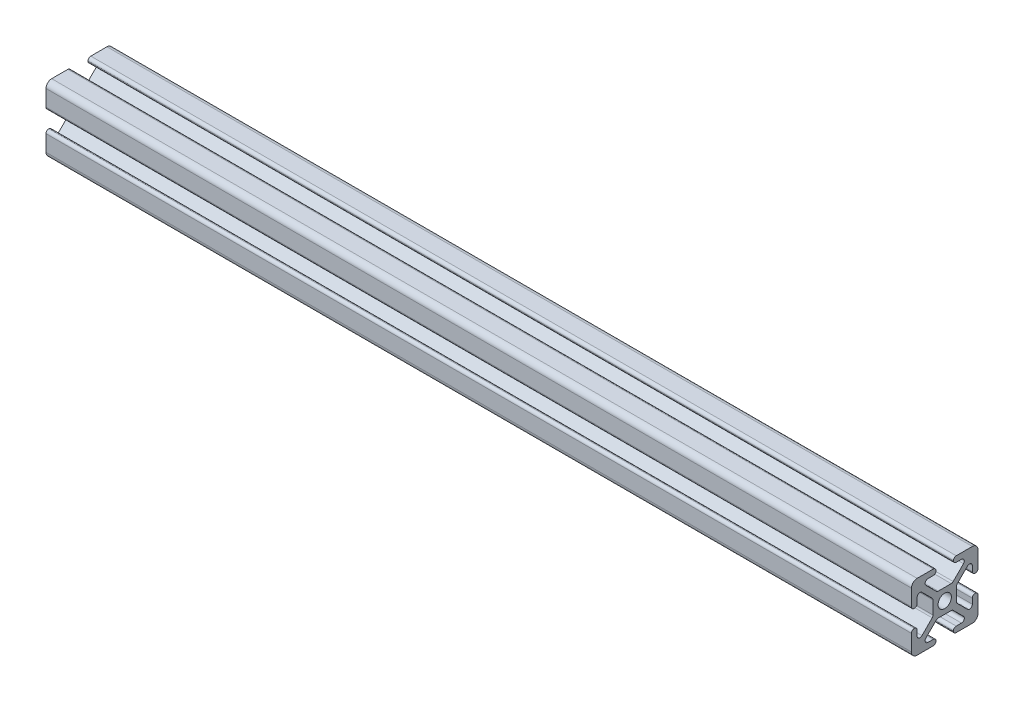
SolidWorks part; units mm, degrees
ref_plane "Front Plane" through (0, 0, 0) normal (1, 0, 0) x (0, 1, 0)
ref_plane "Top Plane" through (0, 0, 0) normal (0, 0, 1) x (0, 1, 0)
ref_plane "Right Plane" through (0, 0, 0) normal (0, 1, 0) x (-1, 0, 0)
sketch "Sketch1" plane through (0, 0, 0) normal (1, 0, 0) x (0, 1, 0)
  line L0 (0, 0) -> (0, 12.5) construction
  line L1 (-12.5, -12.5) -> (12.5, -12.5)
  line L2 (-12.5, -12.5) -> (-12.5, 12.5)
  line L3 (-12.5, 12.5) -> (12.5, 12.5)
  line L4 (12.5, -12.5) -> (12.5, 12.5)
  line L5 (-12.5, -12.5) -> (12.5, 12.5) construction
  line L6 (-12.5, 12.5) -> (12.5, -12.5) construction
  line L7 (-3.25, 12.5) -> (-3.25, 10.37)
  line L8 (-3.25, 10.37) -> (-8.8639, 10.37)
  line L9 (-8.8639, 10.37) -> (-2.8739, 4.38)
  line L10 (-2.8739, 4.38) -> (2.8739, 4.38)
  line L11 (8.8639, 10.37) -> (2.8739, 4.38)
  line L12 (3.25, 10.37) -> (8.8639, 10.37)
  line L13 (3.25, 12.5) -> (3.25, 10.37)
  line L14 (12.5, -3.25) -> (10.37, -3.25)
  line L15 (10.37, -3.25) -> (10.37, -8.8639)
  line L16 (10.37, -8.8639) -> (4.38, -2.8739)
  line L17 (4.38, 2.8739) -> (4.38, -2.8739)
  line L18 (10.37, 8.8639) -> (4.38, 2.8739)
  line L19 (10.37, 3.25) -> (10.37, 8.8639)
  line L20 (12.5, 3.25) -> (10.37, 3.25)
  line L21 (-3.25, -12.5) -> (-3.25, -10.37)
  line L22 (-3.25, -10.37) -> (-8.8639, -10.37)
  line L23 (-8.8639, -10.37) -> (-2.8739, -4.38)
  line L24 (2.8739, -4.38) -> (-2.8739, -4.38)
  line L25 (8.8639, -10.37) -> (2.8739, -4.38)
  line L26 (3.25, -10.37) -> (8.8639, -10.37)
  line L27 (3.25, -12.5) -> (3.25, -10.37)
  line L28 (-12.5, 3.25) -> (-10.37, 3.25)
  line L29 (-10.37, 3.25) -> (-10.37, 8.8639)
  line L30 (-10.37, 8.8639) -> (-4.38, 2.8739)
  line L31 (-4.38, -2.8739) -> (-4.38, 2.8739)
  line L32 (-10.37, -8.8639) -> (-4.38, -2.8739)
  line L33 (-10.37, -3.25) -> (-10.37, -8.8639)
  line L34 (-12.5, -3.25) -> (-10.37, -3.25)
  circle A0 centre (0, 0) radius 2.5
  point P0 (0, 0)
  point P15 (0, 4.38)
  dimension "D3" = 5
  dimension "D1" = 25
  dimension "D2" = 25
  dimension "D4" = 2.13
  dimension "D5" = 2.13
  dimension "D6" = 6.5
  dimension "D7" = 4.38
  dimension "D8" = 4
extrude "Boss-Extrude1" add sketch "Sketch1" along normal blind 325 contours L34 L2 L1 L21 L22 L23 L24 L25 L26 L27 L4 L14 L15 L16 L17 L18 L19 L20 L3 L13 L12 L11 L10 L9 L8 L7 L28 L29 L30 L31 L32 L33 A0 region at (0, -12.1464, -7.875)
fillet "Fillet1" radius 1.065 32 edges at (162.5, -10.37, -8.8639) (162.5, 2.8739, -4.38) (162.5, -2.8739, -4.38) (162.5, -4.38, 2.8739) (162.5, -4.38, -2.8739) (162.5, -2.8739, 4.38) (162.5, 2.8739, 4.38) (162.5, 4.38, 2.8739) (162.5, 4.38, -2.8739) (162.5, -8.8639, -10.37) (162.5, 8.8639, -10.37) (162.5, 10.37, -8.8639) (162.5, -10.37, 8.8639) (162.5, -8.8639, 10.37) (162.5, 10.37, 8.8639) (162.5, 8.8639, 10.37) (162.5, 12.5, 3.25) (162.5, -3.25, -12.5) (162.5, -10.37, 3.25) (162.5, 10.37, 3.25) (162.5, -10.37, -3.25) (162.5, -12.5, -3.25) (162.5, -12.5, 3.25) (162.5, 3.25, -10.37) (162.5, -3.25, -10.37) (162.5, 3.25, -12.5) (162.5, 10.37, -3.25) (162.5, 12.5, -3.25) (162.5, 3.25, 12.5) (162.5, 3.25, 10.37) (162.5, -3.25, 10.37) (162.5, -3.25, 12.5)
fillet "Fillet2" radius 2.13 4 edges at (162.5, 12.5, -12.5) (162.5, -12.5, -12.5) (162.5, 12.5, 12.5) (162.5, -12.5, 12.5)
sketch "Sketch2" plane through (325, 0, 0) normal (1, 0, 0) x (0, 1, 0)
  line L0 (10.37, -12.5) -> (4.315, -12.5)
  line L1 (10.37, -12.5) -> (4.315, -12.5)
  line L2 (4.315, -10.37) -> (6.2927, -10.37)
  line L3 (4.315, -10.37) -> (6.2927, -10.37)
  line L4 (7.0458, -8.5519) -> (3.1858, -4.6919)
  line L5 (7.0458, -8.5519) -> (3.1858, -4.6919)
  line L6 (2.4327, -4.38) -> (-2.4327, -4.38)
  line L7 (2.4327, -4.38) -> (-2.4327, -4.38)
  line L8 (-3.1858, -4.6919) -> (-7.0458, -8.5519)
  line L9 (-3.1858, -4.6919) -> (-7.0458, -8.5519)
  line L10 (-6.2927, -10.37) -> (-4.315, -10.37)
  line L11 (-6.2927, -10.37) -> (-4.315, -10.37)
  line L12 (-4.315, -12.5) -> (-10.37, -12.5)
  line L13 (-4.315, -12.5) -> (-10.37, -12.5)
  line L14 (-12.5, -10.37) -> (-12.5, -4.315)
  line L15 (-12.5, -10.37) -> (-12.5, -4.315)
  line L16 (-10.37, -4.315) -> (-10.37, -6.2927)
  line L17 (-10.37, -4.315) -> (-10.37, -6.2927)
  line L18 (-8.5519, -7.0458) -> (-4.6919, -3.1858)
  line L19 (-8.5519, -7.0458) -> (-4.6919, -3.1858)
  line L20 (-4.38, -2.4327) -> (-4.38, 2.4327)
  line L21 (-4.38, -2.4327) -> (-4.38, 2.4327)
  line L22 (-4.6919, 3.1858) -> (-8.5519, 7.0458)
  line L23 (-4.6919, 3.1858) -> (-8.5519, 7.0458)
  line L24 (-10.37, 6.2927) -> (-10.37, 4.315)
  line L25 (-10.37, 6.2927) -> (-10.37, 4.315)
  line L26 (-12.5, 4.315) -> (-12.5, 10.37)
  line L27 (-12.5, 4.315) -> (-12.5, 10.37)
  line L28 (-10.37, 12.5) -> (-4.315, 12.5)
  line L29 (-10.37, 12.5) -> (-4.315, 12.5)
  line L30 (-4.315, 10.37) -> (-6.2927, 10.37)
  line L31 (-4.315, 10.37) -> (-6.2927, 10.37)
  line L32 (-7.0458, 8.5519) -> (-3.1858, 4.6919)
  line L33 (-7.0458, 8.5519) -> (-3.1858, 4.6919)
  line L34 (-2.4327, 4.38) -> (2.4327, 4.38)
  line L35 (-2.4327, 4.38) -> (2.4327, 4.38)
  line L36 (3.1858, 4.6919) -> (7.0458, 8.5519)
  line L37 (3.1858, 4.6919) -> (7.0458, 8.5519)
  line L38 (6.2927, 10.37) -> (4.315, 10.37)
  line L39 (6.2927, 10.37) -> (4.315, 10.37)
  line L40 (4.315, 12.5) -> (10.37, 12.5)
  line L41 (4.315, 12.5) -> (10.37, 12.5)
  line L42 (12.5, 10.37) -> (12.5, 4.315)
  line L43 (12.5, 10.37) -> (12.5, 4.315)
  line L44 (10.37, 4.315) -> (10.37, 6.2927)
  line L45 (10.37, 4.315) -> (10.37, 6.2927)
  line L46 (8.5519, 7.0458) -> (4.6919, 3.1858)
  line L47 (8.5519, 7.0458) -> (4.6919, 3.1858)
  line L48 (4.38, 2.4327) -> (4.38, -2.4327)
  line L49 (4.38, 2.4327) -> (4.38, -2.4327)
  line L50 (4.6919, -3.1858) -> (8.5519, -7.0458)
  line L51 (4.6919, -3.1858) -> (8.5519, -7.0458)
  line L52 (10.37, -6.2927) -> (10.37, -4.315)
  line L53 (10.37, -6.2927) -> (10.37, -4.315)
  line L54 (12.5, -4.315) -> (12.5, -10.37)
  line L55 (12.5, -4.315) -> (12.5, -10.37)
  arc A0 (10.37, -12.5) -> (12.5, -10.37) centre (10.37, -10.37) ccw
  circle A1 centre (0, 0) radius 2.5
  circle A2 centre (0, 0) radius 2.5
  arc A3 (10.37, -12.5) -> (12.5, -10.37) centre (10.37, -10.37) ccw
  arc A4 (3.25, -11.435) -> (4.315, -12.5) centre (4.315, -11.435) ccw
  arc A5 (3.25, -11.435) -> (4.315, -12.5) centre (4.315, -11.435) ccw
  arc A6 (4.315, -10.37) -> (3.25, -11.435) centre (4.315, -11.435) ccw
  arc A7 (4.315, -10.37) -> (3.25, -11.435) centre (4.315, -11.435) ccw
  arc A8 (6.2927, -10.37) -> (7.0458, -8.5519) centre (6.2927, -9.305) ccw
  arc A9 (6.2927, -10.37) -> (7.0458, -8.5519) centre (6.2927, -9.305) ccw
  arc A10 (3.1858, -4.6919) -> (2.4327, -4.38) centre (2.4327, -5.445) ccw
  arc A11 (3.1858, -4.6919) -> (2.4327, -4.38) centre (2.4327, -5.445) ccw
  arc A12 (-2.4327, -4.38) -> (-3.1858, -4.6919) centre (-2.4327, -5.445) ccw
  arc A13 (-2.4327, -4.38) -> (-3.1858, -4.6919) centre (-2.4327, -5.445) ccw
  arc A14 (-7.0458, -8.5519) -> (-6.2927, -10.37) centre (-6.2927, -9.305) ccw
  arc A15 (-7.0458, -8.5519) -> (-6.2927, -10.37) centre (-6.2927, -9.305) ccw
  arc A16 (-3.25, -11.435) -> (-4.315, -10.37) centre (-4.315, -11.435) ccw
  arc A17 (-3.25, -11.435) -> (-4.315, -10.37) centre (-4.315, -11.435) ccw
  arc A18 (-4.315, -12.5) -> (-3.25, -11.435) centre (-4.315, -11.435) ccw
  arc A19 (-4.315, -12.5) -> (-3.25, -11.435) centre (-4.315, -11.435) ccw
  arc A20 (-12.5, -10.37) -> (-10.37, -12.5) centre (-10.37, -10.37) ccw
  arc A21 (-12.5, -10.37) -> (-10.37, -12.5) centre (-10.37, -10.37) ccw
  arc A22 (-11.435, -3.25) -> (-12.5, -4.315) centre (-11.435, -4.315) ccw
  arc A23 (-11.435, -3.25) -> (-12.5, -4.315) centre (-11.435, -4.315) ccw
  arc A24 (-10.37, -4.315) -> (-11.435, -3.25) centre (-11.435, -4.315) ccw
  arc A25 (-10.37, -4.315) -> (-11.435, -3.25) centre (-11.435, -4.315) ccw
  arc A26 (-10.37, -6.2927) -> (-8.5519, -7.0458) centre (-9.305, -6.2927) ccw
  arc A27 (-10.37, -6.2927) -> (-8.5519, -7.0458) centre (-9.305, -6.2927) ccw
  arc A28 (-4.6919, -3.1858) -> (-4.38, -2.4327) centre (-5.445, -2.4327) ccw
  arc A29 (-4.6919, -3.1858) -> (-4.38, -2.4327) centre (-5.445, -2.4327) ccw
  arc A30 (-4.38, 2.4327) -> (-4.6919, 3.1858) centre (-5.445, 2.4327) ccw
  arc A31 (-4.38, 2.4327) -> (-4.6919, 3.1858) centre (-5.445, 2.4327) ccw
  arc A32 (-8.5519, 7.0458) -> (-10.37, 6.2927) centre (-9.305, 6.2927) ccw
  arc A33 (-8.5519, 7.0458) -> (-10.37, 6.2927) centre (-9.305, 6.2927) ccw
  arc A34 (-11.435, 3.25) -> (-10.37, 4.315) centre (-11.435, 4.315) ccw
  arc A35 (-11.435, 3.25) -> (-10.37, 4.315) centre (-11.435, 4.315) ccw
  arc A36 (-12.5, 4.315) -> (-11.435, 3.25) centre (-11.435, 4.315) ccw
  arc A37 (-12.5, 4.315) -> (-11.435, 3.25) centre (-11.435, 4.315) ccw
  arc A38 (-10.37, 12.5) -> (-12.5, 10.37) centre (-10.37, 10.37) ccw
  arc A39 (-10.37, 12.5) -> (-12.5, 10.37) centre (-10.37, 10.37) ccw
  arc A40 (-3.25, 11.435) -> (-4.315, 12.5) centre (-4.315, 11.435) ccw
  arc A41 (-3.25, 11.435) -> (-4.315, 12.5) centre (-4.315, 11.435) ccw
  arc A42 (-4.315, 10.37) -> (-3.25, 11.435) centre (-4.315, 11.435) ccw
  arc A43 (-4.315, 10.37) -> (-3.25, 11.435) centre (-4.315, 11.435) ccw
  arc A44 (-6.2927, 10.37) -> (-7.0458, 8.5519) centre (-6.2927, 9.305) ccw
  arc A45 (-6.2927, 10.37) -> (-7.0458, 8.5519) centre (-6.2927, 9.305) ccw
  arc A46 (-3.1858, 4.6919) -> (-2.4327, 4.38) centre (-2.4327, 5.445) ccw
  arc A47 (-3.1858, 4.6919) -> (-2.4327, 4.38) centre (-2.4327, 5.445) ccw
  arc A48 (2.4327, 4.38) -> (3.1858, 4.6919) centre (2.4327, 5.445) ccw
  arc A49 (2.4327, 4.38) -> (3.1858, 4.6919) centre (2.4327, 5.445) ccw
  arc A50 (7.0458, 8.5519) -> (6.2927, 10.37) centre (6.2927, 9.305) ccw
  arc A51 (7.0458, 8.5519) -> (6.2927, 10.37) centre (6.2927, 9.305) ccw
  arc A52 (3.25, 11.435) -> (4.315, 10.37) centre (4.315, 11.435) ccw
  arc A53 (3.25, 11.435) -> (4.315, 10.37) centre (4.315, 11.435) ccw
  arc A54 (4.315, 12.5) -> (3.25, 11.435) centre (4.315, 11.435) ccw
  arc A55 (4.315, 12.5) -> (3.25, 11.435) centre (4.315, 11.435) ccw
  arc A56 (12.5, 10.37) -> (10.37, 12.5) centre (10.37, 10.37) ccw
  arc A57 (12.5, 10.37) -> (10.37, 12.5) centre (10.37, 10.37) ccw
  arc A58 (11.435, 3.25) -> (12.5, 4.315) centre (11.435, 4.315) ccw
  arc A59 (11.435, 3.25) -> (12.5, 4.315) centre (11.435, 4.315) ccw
  arc A60 (10.37, 4.315) -> (11.435, 3.25) centre (11.435, 4.315) ccw
  arc A61 (10.37, 4.315) -> (11.435, 3.25) centre (11.435, 4.315) ccw
  arc A62 (10.37, 6.2927) -> (8.5519, 7.0458) centre (9.305, 6.2927) ccw
  arc A63 (10.37, 6.2927) -> (8.5519, 7.0458) centre (9.305, 6.2927) ccw
  arc A64 (4.6919, 3.1858) -> (4.38, 2.4327) centre (5.445, 2.4327) ccw
  arc A65 (4.6919, 3.1858) -> (4.38, 2.4327) centre (5.445, 2.4327) ccw
  arc A66 (4.38, -2.4327) -> (4.6919, -3.1858) centre (5.445, -2.4327) ccw
  arc A67 (4.38, -2.4327) -> (4.6919, -3.1858) centre (5.445, -2.4327) ccw
  arc A68 (8.5519, -7.0458) -> (10.37, -6.2927) centre (9.305, -6.2927) ccw
  arc A69 (8.5519, -7.0458) -> (10.37, -6.2927) centre (9.305, -6.2927) ccw
  arc A70 (11.435, -3.25) -> (10.37, -4.315) centre (11.435, -4.315) ccw
  arc A71 (11.435, -3.25) -> (10.37, -4.315) centre (11.435, -4.315) ccw
  arc A72 (12.5, -4.315) -> (11.435, -3.25) centre (11.435, -4.315) ccw
  arc A73 (12.5, -4.315) -> (11.435, -3.25) centre (11.435, -4.315) ccw
  dimension "D1" = 0
